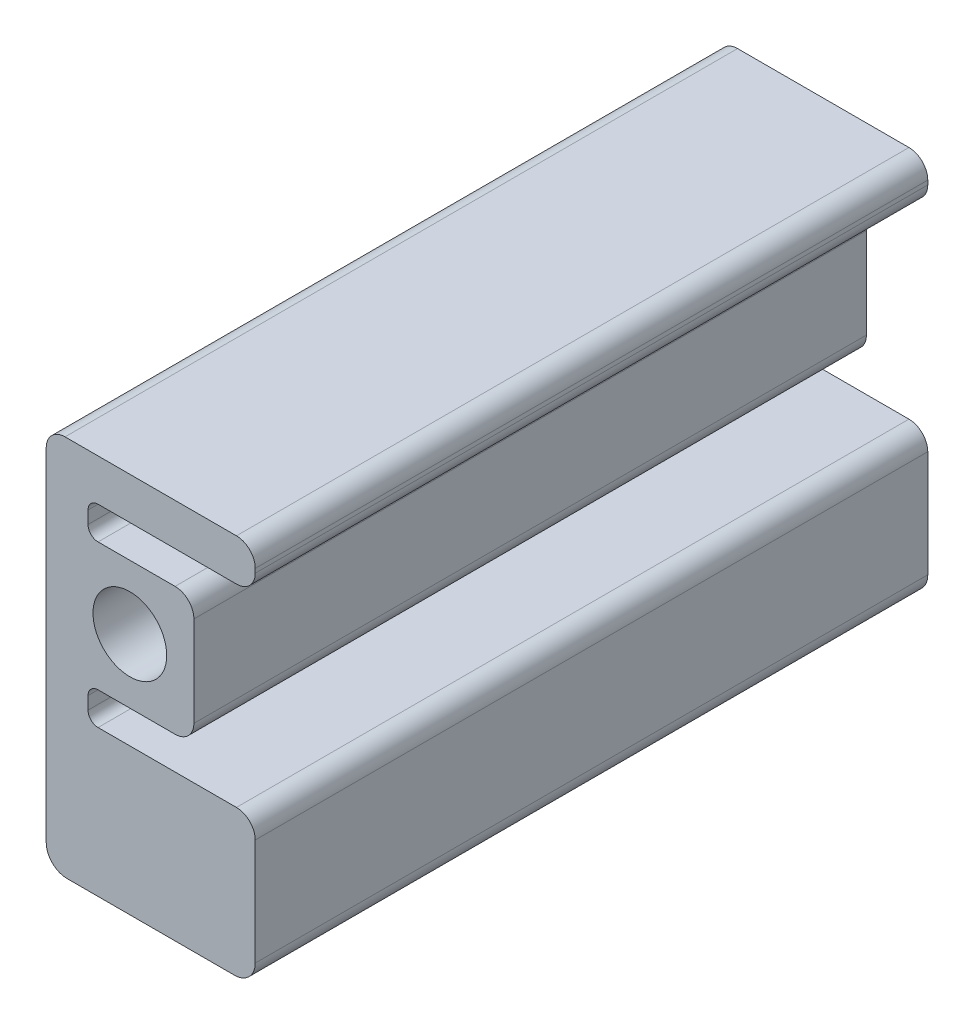
SolidWorks part; units mm, degrees
material "Pink Foam"
ref_plane "Front Plane" through (0, 0, 0) normal (0, 0, 1) x (1, 0, 0)
ref_plane "Top Plane" through (0, 0, 0) normal (0, 1, 0) x (1, 0, 0)
ref_plane "Right Plane" through (0, 0, 0) normal (1, 0, 0) x (0, 0, -1)
sketch "Sketch1" plane through (0, 0, 0) normal (0, 0, 1) x (1, 0, 0)
  line L0 (-25.4, -67.48) -> (-25.4, 36.365)
  line L2 (38.1, -67.48) -> (38.1, -35.095)
  line L3 (32.385, -29.38) -> (-9.652, -29.38)
  line L4 (-12.7, -26.332) -> (-12.7, -22.503)
  line L5 (-9.652, -19.455) -> (0, -19.455)
  line L6 (-9.652, 19.455) -> (0, 19.455)
  line L7 (-12.7, 22.503) -> (-12.7, 26.332)
  line L8 (-9.652, 29.38) -> (32.385, 29.38)
  line L9 (38.1, 35.095) -> (38.1, 36.365)
  line L10 (32.385, 42.08) -> (-19.685, 42.08)
  line L15 (0, -11.2) -> (0, -19.455) construction
  line L16 (0, 11.2) -> (0, 19.455) construction
  line L17 (11.2, 0) -> (19.455, 0) construction
  line L18 (0, 19.455) -> (13.74, 19.455)
  line L19 (19.455, 13.74) -> (19.455, 0)
  line L20 (19.455, 0) -> (19.455, -13.74)
  line L21 (13.74, -19.455) -> (0, -19.455)
  line L24 (31.75, -73.83) -> (-19.05, -73.83)
  circle A0 centre (0, 0) radius 11.2
  arc A3 (-19.685, 42.08) -> (-25.4, 36.365) centre (-19.685, 36.365) ccw
  arc A4 (38.1, 36.365) -> (32.385, 42.08) centre (32.385, 36.365) ccw
  arc A6 (32.385, 29.38) -> (38.1, 35.095) centre (32.385, 35.095) ccw
  arc A7 (38.1, -35.095) -> (32.385, -29.38) centre (32.385, -35.095) ccw
  arc A8 (19.455, -13.74) -> (13.74, -19.455) centre (13.74, -13.74) cw
  arc A9 (13.74, 19.455) -> (19.455, 13.74) centre (13.74, 13.74) cw
  arc A10 (-12.7, 26.332) -> (-9.652, 29.38) centre (-9.652, 26.332) cw
  arc A11 (-9.652, 19.455) -> (-12.7, 22.503) centre (-9.652, 22.503) cw
  arc A12 (-12.7, -22.503) -> (-9.652, -19.455) centre (-9.652, -22.503) cw
  arc A13 (-9.652, -29.38) -> (-12.7, -26.332) centre (-9.652, -26.332) cw
  arc A14 (31.75, -73.83) -> (38.1, -67.48) centre (31.75, -67.48) ccw
  arc A15 (-19.05, -73.83) -> (-25.4, -67.48) centre (-19.05, -67.48) cw
  point P12 (0, 11.2)
  point P20 (0, -11.2)
  point P22 (11.2, 0)
  point P45 (-12.7, 29.38)
  point P48 (-12.7, 19.455)
  point P53 (-12.7, -29.38)
  point P57 (38.1, -73.83)
  point P60 (38.1, -73.83)
  point P63 (-25.4, -73.83)
  dimension "D1" = 22.4
  dimension "D11" = 3.048
  dimension "D9" = 5.715
  dimension "D14" = 5.715
  dimension "D12" = 6.35
  dimension "D2" = 25.4
  dimension "D3" = 8.255
  dimension "D4" = 9.925
  dimension "D5" = 44.45
  dimension "D6" = 9.925
  dimension "D7" = 12.7
  dimension "D8" = 12.7
  dimension "D10" = 63.5
extrude "Boss-Extrude1" add sketch "Sketch1" along normal blind 204.3137
